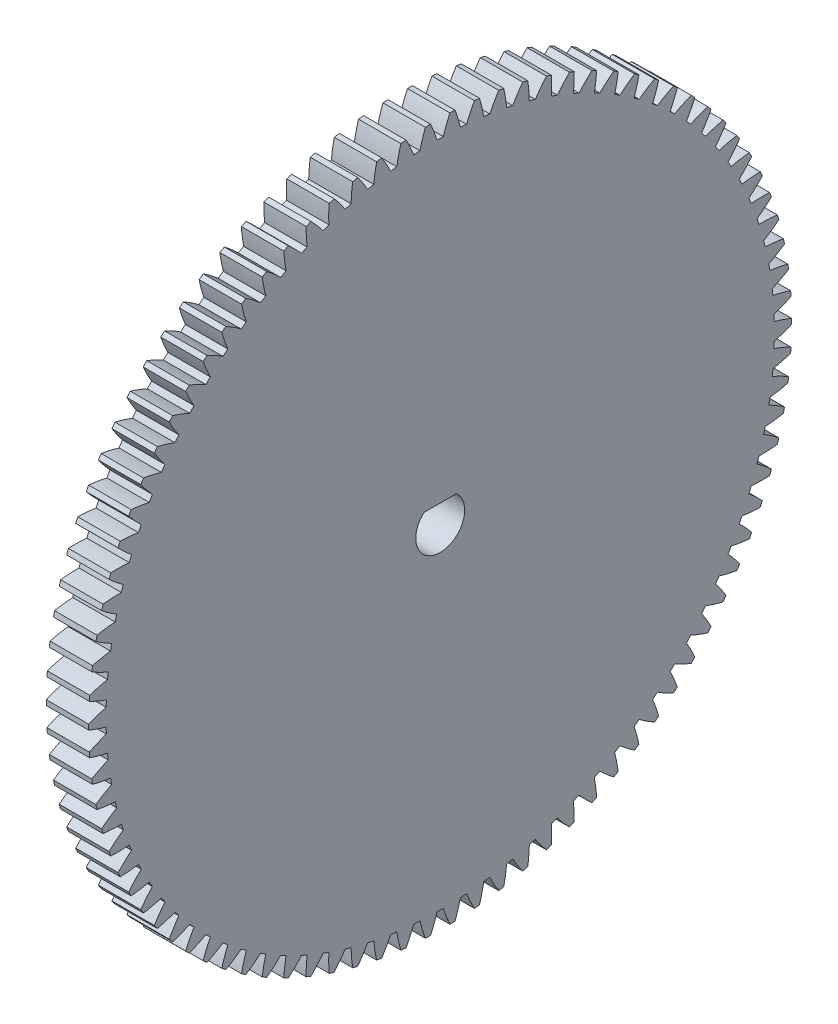
SolidWorks part; units mm, degrees
ref_plane "Plane1" through (0, 0, 0) normal (0, 0, 1) x (1, 0, 0)
ref_plane "Plane2" through (0, 0, 0) normal (0, 1, 0) x (1, 0, 0)
ref_plane "Plane3" through (0, 0, 0) normal (1, 0, 0) x (0, 0, -1)
sketch "HoldingSke" plane through (0, 0, 0) normal (0, 1, 0) x (1, 0, 0)
  line L0 (0, 0) -> (0, -812.8)
  line L1 (-15, 0) -> (100, 0) construction
  line L2 (0, 0) -> (-2.1039, 2.3779)
  line L3 (0, 0) -> (-11.863, 4.5341)
  line L4 (0, 0) -> (0, 8.636)
  line L5 (0, 0) -> (-47.5972, -17.7524)
  line L6 (0, 0) -> (-3.6532, -2.4648)
  line L7 (-2.1039, 2.3779) -> (8.8308, 51.9871)
  line L8 (-76.2, 54.61) -> (-71.1708, 54.61)
  line L9 (-71.009, 38.7566) -> (-53.1078, 45.2721)
  line L10 (-76.2, 71.12) -> (104.1128, 71.12)
  line L11 (0, 0) -> (-4.4069, 0)
  line L12 (-76.2, 101.6) -> (-76.1716, 101.6)
  line L13 (24.9733, 27.94) -> (52.9518, 28.4284)
  line L14 (24.9733, 27.94) -> (25.0241, 27.9398)
  line L15 (24.9733, 27.94) -> (100.4021, 29.52)
  circle A0 centre (0, 0) radius 2.3812
  circle A1 centre (0, 0) radius 34.7154
  circle A2 centre (0, 0) radius 38.1
  circle A3 centre (0, 0) radius 2.3812
  dimension "Num_teeth" = 90
  dimension "H" = 19.05
  dimension "Pitch_radius" = 180.3128
  dimension "Width" = 4.4069
  dimension "Thickness" = 4.4069
sketch "BasProSke" plane through (0, 0, 0) normal (0, 1, 0) x (1, 0, 0)
  line L0 (-10, 0) -> (60, 0) construction
  line L1 (0, 0) -> (0, 36.5125)
  line L2 (0, 0) -> (4.4069, 0)
  line L3 (4.4069, 0) -> (4.4069, 36.5125)
  line L4 (4.4069, 36.5125) -> (0, 36.5125)
  dimension "Thickness" = 4.4069
  dimension "Diameter" = 73.025
revolve "Base-Revolve" add sketch "BasProSke" angle 360 about L0
sketch "TooCutSke" plane through (0, 0, 0) normal (1, 0, 0) x (0, 0, -1)
  line L1 (0, 0) -> (0, 107) construction
  line L2 (0, 0) -> (-0.6732, 35.7124) construction
  line L3 (0, 0) -> (-2.4928, 71.3848) construction
  line L4 (-0.6732, 35.7124) -> (-1.2464, 35.6924) construction
  arc A0 (0.3251, 34.7139) -> (-0.3251, 34.7139) centre (0, 0) ccw
  arc A1 (1.0193, 36.5237) -> (-1.0193, 36.5237) centre (0, 0) ccw
  circle A2 centre (0, 0) radius 35.7188 construction
  circle A3 centre (0, 0) radius 33.5646 construction
  arc A4 (-0.3251, 34.7139) -> (-1.0193, 36.5237) centre (-13.9814, 30.514) ccw
  arc A5 (1.0193, 36.5237) -> (0.3251, 34.7139) centre (13.9814, 30.514) ccw
extrude "ToothCut" cut sketch "TooCutSke" along normal through all
fillet "Breaks" [suppressed] radius 0.0159 tangent propagation no
fillet "RootFillets" [suppressed] radius 0.2095
pattern_circular "TeethCuts" count 90 every 4 about axis through (-10, 0, 0) along (1, 0, 0) of "ToothCut", "RootFillets", "Breaks"
sketch "HubNeaOneSke" plane through (0, 0, 0) normal (-1, 0, 0) x (0, 0, 1)
  circle A0 centre (0, 0) radius 34.7154
  dimension "Diameter" = 69.4309
extrude "HubNearOne" [suppressed] add sketch "HubNeaOneSke" along normal blind 46.3932
sketch "HubNeaBotSke" plane through (0, 0, 0) normal (-1, 0, 0) x (0, 0, 1)
  circle A0 centre (0, 0) radius 34.7154
  dimension "Diameter" = 69.4309
extrude "HubNearBoth" [suppressed] add sketch "HubNeaBotSke" along normal blind 23.1966
ref_plane "FarPln" through (4.4069, 0, 0) normal (1, 0, 0) x (0, 0, -1)
sketch "HubFarSke" plane through (4.4069, 0, 0) normal (1, 0, 0) x (0, 0, -1)
  circle A0 centre (0, 0) radius 34.7154
  dimension "Diameter" = 69.4309
extrude "HubFar" [suppressed] add sketch "HubFarSke" along normal blind 23.1966
sketch "BorSke" plane through (0, 0, 0) normal (1, 0, 0) x (0, 0, -1)
  line L0 (-1.6801, 1.905) -> (1.6801, 1.905)
  arc A0 (-1.6801, 1.905) -> (1.6801, 1.905) centre (0, 0) ccw
  point P4 (0, 1.905)
  point P5 (0, 2.54)
  dimension "D1" = 0.635
  dimension "Diameter" = 5.08
extrude "Bore" cut sketch "BorSke" along normal mid plane 101.6001
sketch "KeySke" plane through (0, 0, 0) normal (1, 0, 0) x (0, 0, -1)
  line L0 (-0.127, 0) -> (-0.127, 2.6479)
  line L1 (-0.127, 2.6479) -> (0.127, 2.6479)
  line L2 (0.127, 2.6479) -> (0.127, 0)
  line L3 (0, 0) -> (0, 34) construction
  line L4 (-0.127, 0) -> (0.127, 0)
  dimension "Width" = 0.254
extrude "Keyway" [suppressed] cut sketch "KeySke" along normal mid plane 101.6001
pattern_circular "Keyway2" [suppressed] count 2 every 90 about axis through (-10, 0, 0) along (1, 0, 0)
equation "' \"Pitch@HoldingSke\" = 4"
equation "' \"Num_teeth@HoldingSke\" = 12"
equation "' \"Ap@HoldingSke\" =  20"
equation "' \"Ap@HoldingSke\" = 20"
equation "' \"Width@HoldingSke\" = 0.5"
equation "' \"Hub_dia@HoldingSke\"= 1"
equation "' \"Hub_dia@HoldingSke\" = 1"
equation "' \"Overall_len@HoldingSke\" = 1.0"
equation "' \"Bore@HoldingSke\" = 0.75"
equation "' \"T_dim@HoldingSke\" = 0.85"
equation "' \"Width@KeySke\" = 0.25"
equation "' \"Show_teeth@HoldingSke\" = 13"
equation "' \"Backlash@HoldingSke\" = 0.009"
equation "' \"Addendum_fac@HoldingSke\" = 1.0"
equation "' \"Dedendum_fac@HoldingSke\" = 1.25"
equation "' \"Dedendum_add@HoldingSke\" = 0.00005"
equation "' \"Clearance_fac@HoldingSke\" = 0.25"
equation "' \"Pitch@HoldingSke\" = 0.5"
equation "' \"Num_teeth@HoldingSke\" = 23"
equation "' \"Show_teeth@HoldingSke\" = 23"
equation "' \"Backlash@HoldingSke\" = 0.0375"
equation "\"Overcut_dia@TooCutSke\" = (\"Num_teeth@HoldingSke\" + 2 * \"Addendum_fac@HoldingSke\") / \"Pitch@HoldingSke\" + 0.002"
equation "\"Pitch_dia@TooCutSke\" = \"Num_teeth@HoldingSke\" / \"Pitch@HoldingSke\""
equation "\"Base_dia@TooCutSke\" = \"Num_teeth@HoldingSke\" / \"Pitch@HoldingSke\" * cos((\"Ap@HoldingSke\"  * 3.14159265 / 180))"
equation "\"Root_dia@TooCutSke\" = (\"Num_teeth@HoldingSke\" + 2) / \"Pitch@HoldingSke\" - 2 * (\"Addendum_fac@HoldingSke\" + \"Dedendum_fac@HoldingSke\") / \"Pitch@HoldingSke\" - \"Dedendum_add@HoldingSke\" * 2"
equation "\"Half_ang@TooCutSke\" = 180 / \"Num_teeth@HoldingSke\""
equation "\"Half_CT@TooCutSke\" = \"Num_teeth@HoldingSke\" / \"Pitch@HoldingSke\" * sin((3.14159265 / 2 / \"Num_teeth@HoldingSke\")) / 2 - 7 * \"Backlash@HoldingSke\" / 4"
equation "\"Flank_rad@TooCutSke\" = \"Num_teeth@HoldingSke\" / \"Pitch@HoldingSke\" / 5"
equation "\"Radius@RootFillets\" = \"Clearance_fac@HoldingSke\" / \"Pitch@HoldingSke\" + \"Dedendum_add@HoldingSke\""
equation "\"Break_rad@Breaks\" = 0.02 / \"Pitch@HoldingSke\""
equation "\"Thickness@HoldingSke\" = \"Width@HoldingSke\""
equation "\"OAL@HoldingSke\" = \"Thickness@HoldingSke\""
equation "\"MHD@HoldingSke\" = (\"Num_teeth@HoldingSke\" + 2) / \"Pitch@HoldingSke\" - 2 * (\"Addendum_fac@HoldingSke\" + \"Dedendum_fac@HoldingSke\")  / \"Pitch@HoldingSke\" - \"Dedendum_add@HoldingSke\" * 2"
equation "\"MBD@HoldingSke\" = (\"Num_teeth@HoldingSke\" + 2) / \"Pitch@HoldingSke\" - 2 * (\"Addendum_fac@HoldingSke\" + \"Dedendum_fac@HoldingSke\")  / \"Pitch@HoldingSke\" - \"Dedendum_add@HoldingSke\" * 2 - 0.002"
equation "\"MHD@HoldingSke\" = ((sgn( \"MHD@HoldingSke\" - \"Hub_dia@HoldingSke\" )-1)*( \"MHD@HoldingSke\" - \"Hub_dia@HoldingSke\" ))/-2+ \"Hub_dia@HoldingSke\""
equation "\"MBD@HoldingSke\" = ((sgn( \"MBD@HoldingSke\" - \"Bore@HoldingSke\" )-1)*( \"MBD@HoldingSke\" - \"Bore@HoldingSke\" ))/-2+ \"Bore@HoldingSke\""
equation "\"OAL@HoldingSke\" = ((sgn( \"OAL@HoldingSke\" - \"Overall_len@HoldingSke\" )+1)*( \"OAL@HoldingSke\" - \"Overall_len@HoldingSke\" ))/2 + \"Overall_len@HoldingSke\" + 0.000002"
equation "\"Num_teeth@TeethCuts\" = int( \"Show_teeth@HoldingSke\" ) + 1"
equation "\"Num_teeth@TeethCuts\" = ((sgn( \"Num_teeth@TeethCuts\" - \"Num_teeth@HoldingSke\" )-1)*( \"Num_teeth@TeethCuts\" - \"Num_teeth@HoldingSke\" ))/-2+ \"Num_teeth@HoldingSke\""
equation "\"Num_teeth@TeethCuts\" = ((sgn( \"Num_teeth@TeethCuts\" - 2.0)+1)*( \"Num_teeth@TeethCuts\" - 2.0))/2 +2.0"
equation "\"Angle@TeethCuts\" = 360.0 / \"Num_teeth@HoldingSke\""
equation "\"Diameter@BasProSke\" = (\"Num_teeth@HoldingSke\" + 2 * \"Addendum_fac@HoldingSke\") / \"Pitch@HoldingSke\""
equation "\"Thickness@BasProSke\"  = \"Thickness@HoldingSke\""
equation "' \"Fillet_rad@BasProSke\" =  \"Thickness@HoldingSke\" * 0.05"
equation "' \"Fillet_rad@BasProSke\" = \"Thickness@HoldingSke\" * 0.05"
equation "\"MHD@HoldingSke\" = ((sgn( \"MHD@HoldingSke\" - \"Root_dia@TooCutSke\" )-1)*( \"MHD@HoldingSke\" - \"Root_dia@TooCutSke\" ))/-2+ \"Root_dia@TooCutSke\""
equation "\"Diameter@HubNeaOneSke\" = \"MHD@HoldingSke\""
equation "\"Length@HubNearOne\" = \"OAL@HoldingSke\" - \"Thickness@BasProSke\""
equation "\"Diameter@HubNeaBotSke\" = \"MHD@HoldingSke\""
equation "\"Length@HubNearBoth\" = ( \"OAL@HoldingSke\" - \"Thickness@BasProSke\" ) / 2.0"
equation "\"Thickness@FarPln\" = \"Thickness@BasProSke\""
equation "\"Diameter@HubFarSke\" = \"MHD@HoldingSke\""
equation "\"Length@HubFar\" = ( \"OAL@HoldingSke\" - \"Thickness@BasProSke\" ) / 2.0"
equation "\"D1@Bore\" = \"OAL@HoldingSke\" * 2.0"
equation "\"D1@Keyway\" = \"OAL@HoldingSke\" * 2.0"
equation "\"Offset@KeySke\" = \"T_dim@HoldingSke\" - \"MBD@HoldingSke\" / 2.0"
